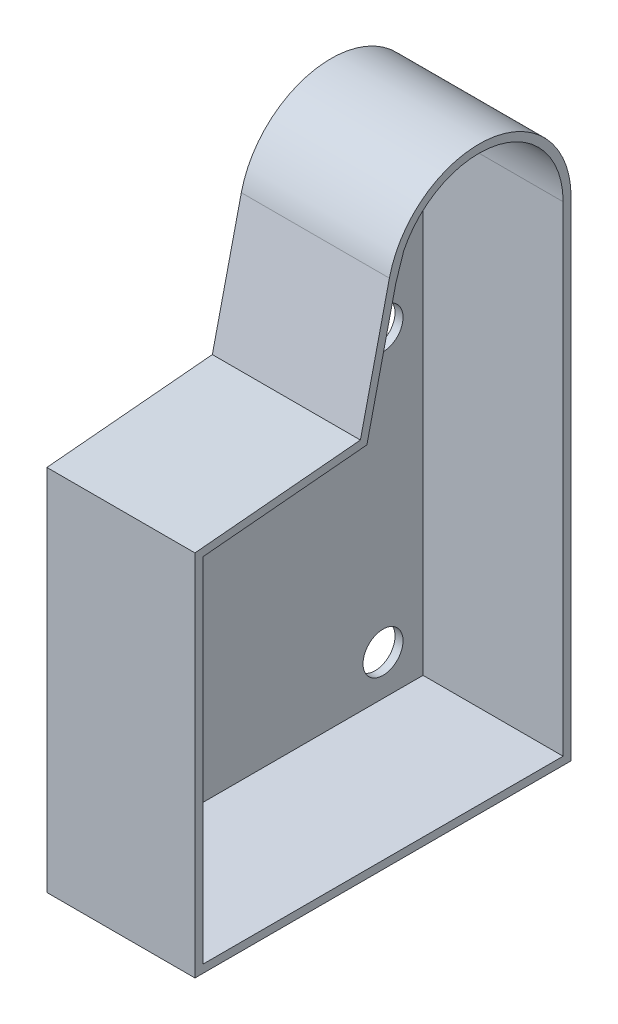
SolidWorks part; units mm, degrees
ref_plane "Front Plane" through (0, 0, 0) normal (0, 0, 1) x (1, 0, 0)
ref_plane "Top Plane" through (0, 0, 0) normal (0, 1, 0) x (1, 0, 0)
ref_plane "Right Plane" through (0, 0, 0) normal (1, 0, 0) x (0, 0, -1)
sketch "Sketch1" plane through (0, 0, 0) normal (1, 0, 0) x (0, 0, -1)
  line L0 (49.0439, -59.7372) -> (-44.9561, -59.7372)
  line L5 (-44.9561, -59.7372) -> (-44.9561, 32.2628)
  line L6 (49.0439, -59.7372) -> (49.0439, 62.2628)
  line L7 (3.632, 67.4307) -> (-3.612, 36.0147)
  line L8 (-44.9561, 32.2628) -> (-3.612, 36.0147)
  line L10 (11.7359, 65.5621) -> (-5.8966, -10.9062) construction
  arc A0 (49.0439, 62.2628) -> (3.632, 67.4307) centre (26.0439, 62.2628) ccw
  circle A2 centre (37.0439, 22.2628) radius 5
  circle A3 centre (37.0439, -47.7372) radius 5
  circle A4 centre (-32.9561, -47.7372) radius 5
  circle A5 centre (-32.9561, 22.2628) radius 5
  point P0 (0, 0)
extrude "Boss-Extrude1" add sketch "Sketch1" against normal blind 2
sketch "Sketch2" plane through (0, 0, 0) normal (1, 0, 0) x (0, 0, -1)
  line L0 (49.0439, -59.7372) -> (-44.9561, -59.7372)
  line L1 (-44.9561, -59.7372) -> (-44.9561, 32.2628)
  line L2 (-3.612, 36.0147) -> (-44.9561, 32.2628) construction
  line L4 (-3.612, 36.0147) -> (3.632, 67.4307)
  line L5 (49.0439, -59.7372) -> (49.0439, 62.2628)
  line L6 (47.0439, -57.7372) -> (-42.9561, -57.7372)
  line L7 (-42.9561, -57.7372) -> (-42.9561, 30.4361)
  line L8 (-42.9561, 30.4361) -> (-1.9887, 34.1538)
  line L9 (-1.9887, 34.1538) -> (5.2554, 65.5698)
  line L10 (47.0439, -57.7372) -> (47.0439, 62.2628)
  line L11 (5.2554, 65.5698) -> (7.22, 71.5719)
  arc A0 (49.0439, 62.2628) -> (3.632, 67.4307) centre (26.0439, 62.2628) ccw
  arc A1 (49.0439, 62.2628) -> (3.632, 67.4307) centre (26.0439, 62.2628) ccw construction
  arc A2 (47.0439, 62.2628) -> (7.22, 71.5719) centre (26.0439, 62.2628) ccw
  dimension "D6" = 2
  dimension "D1" = 2
  dimension "D2" = 2
  dimension "D3" = 2
  dimension "D4" = 2
  dimension "D5" = 2
extrude "Extrude-Thin1" add sketch "Sketch2" along normal blind 35 thin contours L4 A0 L5 L0 L1 | L9 L11 A2 L10 L6 L7 L8 thin type one direction wall 2
